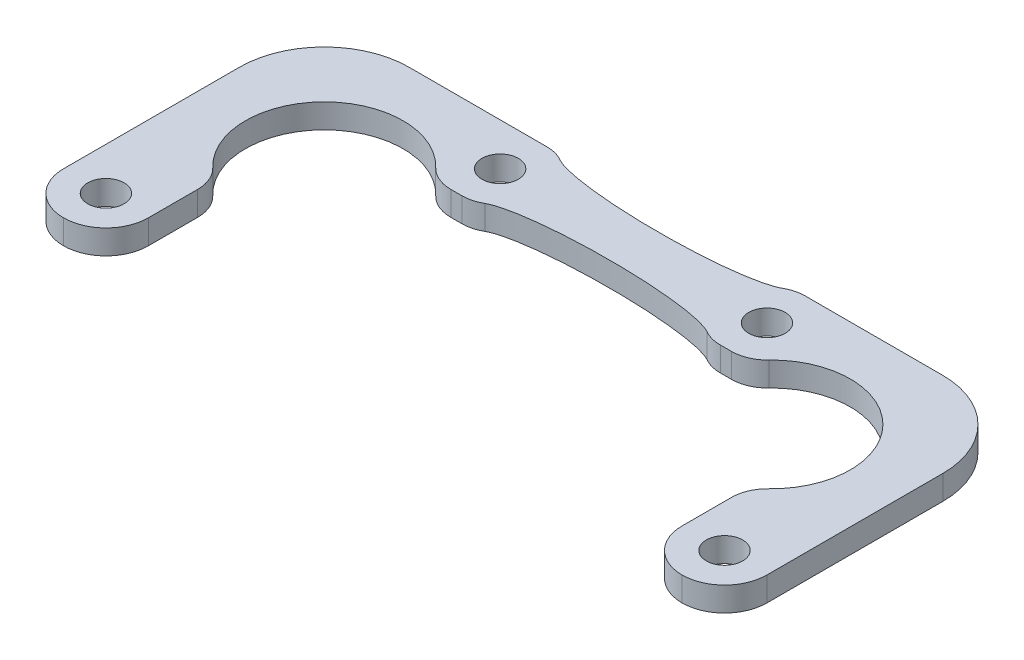
SolidWorks part; units mm, degrees
ref_plane "Front" through (0, 0, 0) normal (0, 0, 1) x (1, 0, 0)
ref_plane "Top" through (0, 0, 0) normal (0, 1, 0) x (1, 0, 0)
ref_plane "Right" through (0, 0, 0) normal (1, 0, 0) x (0, 0, -1)
sketch "Sketch1" plane through (0, 0, 0) normal (0, 1, 0) x (1, 0, 0)
  line L0 (22, 0) -> (-22, 0)
  line L1 (-22, 0) -> (-22, -18)
  line L2 (-22, -18) -> (-29, -18)
  line L3 (-29, -18) -> (-29, 7)
  line L4 (-29, 7) -> (29, 7)
  line L5 (0, 7) -> (0, 0)
  line L6 (29, -18) -> (29, 7)
  line L7 (22, -18) -> (29, -18)
  line L8 (22, 0) -> (22, -18)
  circle A0 centre (-25.5, -14.5) radius 1.5
  circle A1 centre (-11, 3.5) radius 1.5
  circle A2 centre (11, 3.5) radius 1.5
  circle A3 centre (25.5, -14.5) radius 1.5
  dimension "D5" = 3
  dimension "D8" = 3
  dimension "D1" = 29
  dimension "D2" = 7
  dimension "D3" = 7
  dimension "D4" = 25
  dimension "D6" = 3.5
  dimension "D7" = 3.5
  dimension "D9" = 3.5
  dimension "D10" = 14.5
extrude "Extrude1" add sketch "Sketch1" along normal blind 2 contours L5 L4 L3 L2 L1 L0 A1 A0 | L0 L8 L7 L6 L4 L5 A2 A3
fillet "Fillet1" radius 3 2 edges at (22, 1, 0) (-22, 1, 0)
fillet "Fillet2" radius 3.5 4 edges at (29, 1, 18) (22, 1, 18) (-22, 1, 18) (-29, 1, 18)
sketch "Sketch2" plane through (0, 2, 0) normal (0, 1, 0) x (1, 0, 0)
  line L0 (-29, 7) -> (29, 7) construction
  line L1 (-9.5, 7) -> (9.5, 7)
  ellipse E0 centre (0, 7) end of major axis (-9.5, 7) minor radius 1.5 (-9.5, 7) -> (9.5, 7) ccw
  dimension "D1" = 1.5
  dimension "D2" = 19
ref_plane "Plane1" through (0, 0, -3.5) normal (0, 0, -1) x (-1, 0, 0)
extrude "Extrude2" cut sketch "Sketch2" against normal up to surface (2 mm away) up to face at (-11, 0, -2)
mirror "Mirror1" about plane through (0, 0, -3.5) normal (0, 0, -1) of "Extrude2"
sketch "Sketch3" plane through (0, 2, 0) normal (0, 1, 0) x (-1, 0, 0)
  line L0 (-19, 0) -> (-9.5, 0) construction
  line L1 (-22, 3) -> (-22, 14.5) construction
  line L2 (-13, 0) -> (-19, 0)
  line L3 (-22, 3) -> (-22, 9)
  arc A0 (-13, 0) -> (-22, 9) centre (-18.4354, 3.5646) cw
  arc A1 (-19, 0) -> (-22, 3) centre (-19, 3) cw
  dimension "D3" = 6.5
  dimension "D1" = 6
  dimension "D2" = 6
extrude "Extrude3" cut sketch "Sketch3" against normal up to surface (2 mm away) up to face at (25.5, 0, 16)
mirror "Mirror4" about plane through (0, 0, 0) normal (1, 0, 0) of "Extrude3"
fillet "Fillet3" radius 3 8 edges at (9.5, 1, 0) (-9.5, 1, 0) (22, 1, 9) (13, 1, 0) (-9.5, 1, -7) (9.5, 1, -7) (-22, 1, 9) (-13, 1, 0)
fillet "Fillet5" radius 7 2 edges at (-29, 1, -7) (29, 1, -7)
